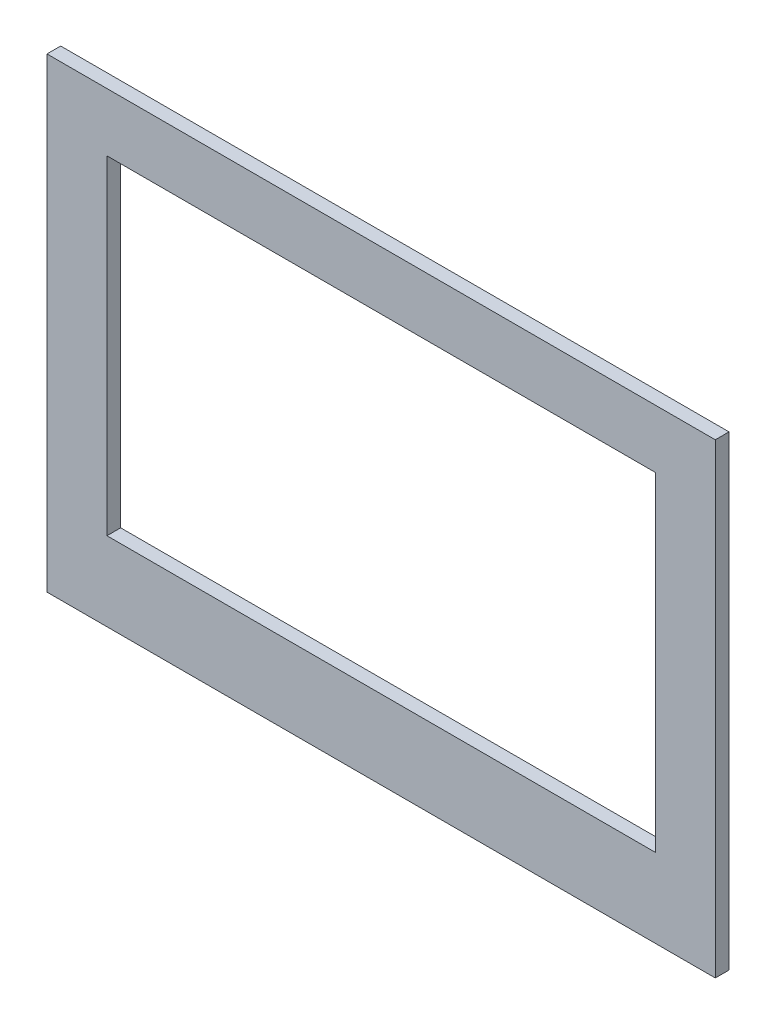
SolidWorks part; units mm, degrees
ref_plane "Front Plane" through (0, 0, 0) normal (0, 0, 1) x (1, 0, 0)
ref_plane "Top Plane" through (0, 0, 0) normal (0, 1, 0) x (1, 0, 0)
ref_plane "Right Plane" through (0, 0, 0) normal (1, 0, 0) x (0, 0, -1)
sketch "Sketch1" plane through (0, 0, 0) normal (0, 0, 1) x (1, 0, 0)
  line L1 (85.5, -56) -> (-85.5, -56)
  line L2 (85.5, -56) -> (85.5, 56)
  line L3 (85.5, 56) -> (-85.5, 56)
  line L4 (-85.5, -56) -> (-85.5, 56)
  line L5 (85.5, -56) -> (-85.5, 56) construction
  line L6 (85.5, 56) -> (-85.5, -56) construction
  line L11 (80, -45) -> (-80, -45)
  line L12 (80, -45) -> (80, 51)
  line L13 (80, 51) -> (-80, 51)
  line L14 (-80, -45) -> (-80, 51)
  line L15 (80, -45) -> (-80, 51) construction
  line L16 (80, 51) -> (-80, -45) construction
  line L17 (-14.5, -56) -> (14.5, -56)
  line L18 (-14.5, -56) -> (-14.5, -59)
  line L19 (-14.5, -59) -> (14.5, -59)
  line L20 (14.5, -56) -> (14.5, -59)
  line L21 (97.5, 68) -> (-97.5, 68)
  line L22 (97.5, 68) -> (97.5, -68)
  line L23 (97.5, -68) -> (-97.5, -68)
  line L24 (-97.5, 68) -> (-97.5, -68)
  line L25 (97.5, 68) -> (-97.5, -68) construction
  line L26 (97.5, -68) -> (-97.5, 68) construction
  point P0 (0, 0)
  point P6 (0, 0)
  point P7 (0, 3)
  point P16 (0, 0)
  dimension "D1" = 171
  dimension "D2" = 112
  dimension "D3" = 96
  dimension "D4" = 160
  dimension "D5" = 5
  dimension "D6" = 71
  dimension "D7" = 29
  dimension "D8" = 3
  dimension "D9" = 12
  dimension "D10" = 17.5
  dimension "D11" = 12
extrude "Boss-Extrude1" add sketch "Sketch1" against normal blind 2 contours L4 L1 L2 L3 L11 L14 L13 L12 | L21 L24 L23 L22 L1 L20 L19 L18 L4 L3 L2 | L20 L1 L18 L19 region at (50, -53.9559, 0) region at (0, -57.5, 0) region at (95.1226, 0, 0)
extrude "Boss-Extrude2" add sketch "Sketch1<3>" along normal blind 2 contours L21 L24 L23 L22 L1 L20 L19 L18 L4 L3 L2 | L4 L1 L2 L3 L11 L14 L13 L12 | L20 L1 L18 L19 region at (50, -53.9559, 0) region at (0, -57.5, 0) region at (95.1226, 0, 0)
sketch "Sketch1<3>" plane through (0, 0, 0) normal (0, 0, 1) x (1, 0, 0) same geometry as "Sketch1"
ref_plane "Plane1" through (0, 0, 0) normal (0, 0, 1) x (1, 0, 0)
sketch "Sketch2" plane through (0, 0, 0) normal (0, 0, 1) x (1, 0, 0)
  line L0 (97.5, 68) -> (-97.5, 68) construction
  line L1 (90.5, -61) -> (-90.5, -61) construction
  line L2 (90.5, -61) -> (90.5, 61) construction
  line L3 (90.5, 61) -> (-90.5, 61) construction
  line L4 (-90.5, -61) -> (-90.5, 61) construction
  line L5 (90.5, -61) -> (-90.5, 61) construction
  line L6 (90.5, 61) -> (-90.5, -61) construction
  line L7 (-97.5, 68) -> (-97.5, -68) construction
  line L8 (-90.5, 61) -> (-30.1667, 61) construction
  line L9 (-30.1667, 61) -> (30.1667, 61) construction
  line L10 (30.1667, 61) -> (90.5, 61) construction
  line L11 (-90.5, 61) -> (-30.1667, 61) construction
  line L12 (-30.1667, 61) -> (30.1667, 61) construction
  line L13 (30.1667, 61) -> (90.5, 61) construction
  line L14 (90.5, 61) -> (90.5, 0) construction
  line L15 (90.5, 0) -> (90.5, -61) construction
  circle A0 centre (-90.5, 61) radius 3.25
  circle A2 centre (90.5, 61) radius 3.25
  circle A6 centre (-30.1667, -61) radius 3.25
  circle A7 centre (30.1667, -61) radius 3.25
  circle A8 centre (90.5, 0) radius 3.25
  circle A9 centre (-30.1667, 61) radius 3.25
  circle A10 centre (30.1667, 61) radius 3.25
  circle A11 centre (-90.5, 0) radius 3.25
  point P0 (0, 0)
  dimension "D1" = 6.5
  dimension "D2" = 7
  dimension "D3" = 7
extrude "Cut-Extrude1" cut sketch "Sketch2" against normal blind 1.375 and the other way blind 1.375
